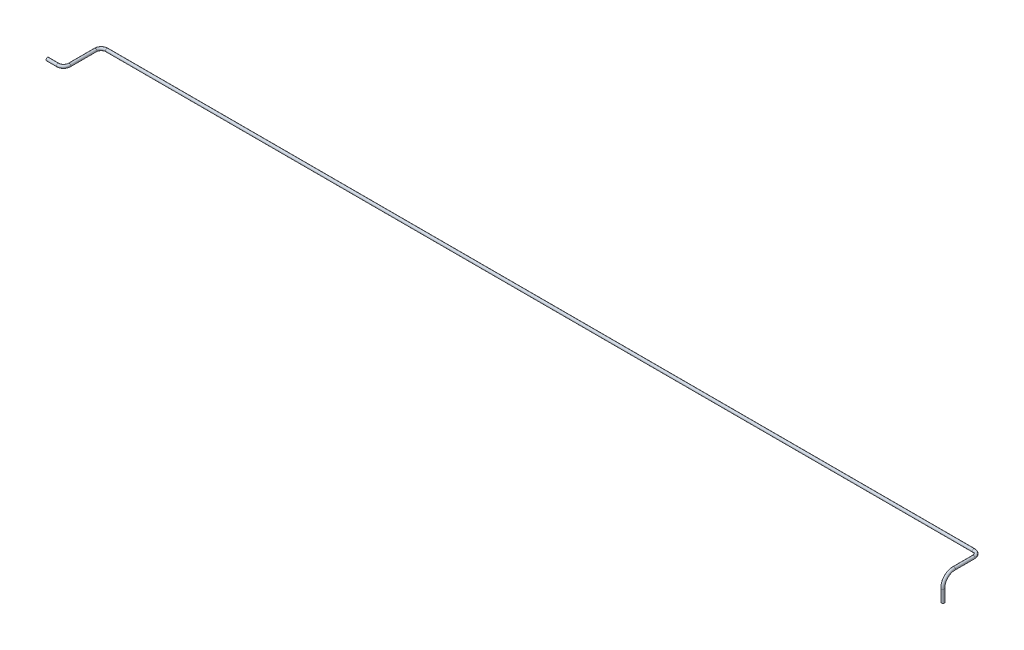
SolidWorks part; units mm, degrees
ref_plane "Front Plane" through (0, 0, 0) normal (0, 0, 1) x (1, 0, 0)
ref_plane "Top Plane" through (0, 0, 0) normal (0, 1, 0) x (1, 0, 0)
ref_plane "Right Plane" through (0, 0, 0) normal (1, 0, 0) x (0, 0, -1)
sketch3d "3DSketch1"
  line L1 (0, 0, 0) -> (22.86, 0, 0)
  line L2 (35.56, 0, -12.7) -> (35.56, 0, -69.85)
  line L3 (48.26, 0, -82.55) -> (1952.9674, 0, -82.55)
  line L4 (1965.6674, 0, -69.85) -> (1965.6674, 0, -26.7385)
  line L5 (1966.5416, -24.9414, -1.3424) -> (1967.4465, -50.7611, -0.8914)
  arc A0 (1965.6674, 0, -69.85) -> (1952.9674, 0, -82.55) centre (1952.9674, 0, -69.85) ccw
  arc A1 (35.56, 0, -69.85) -> (48.26, 0, -82.55) centre (48.26, 0, -69.85) ccw
  arc A2 (22.86, 0, 0) -> (35.56, 0, -12.7) centre (22.86, 0, -12.7) ccw
  arc A3 (1965.6674, 0, -26.7385) -> (1966.5416, -24.9414, -1.3424) centre (1966.5571, -25.3844, -26.7385) ccw
  point P9 (1965.6674, 0, -82.55)
  point P10 (1952.9674, 12.7, -69.85)
  point P12 (1965.6674, 0, -1.778)
  point P16 (35.56, 0, -82.55)
  point P17 (48.26, -12.7, -69.85)
  point P20 (35.56, 0, 0)
  point P22 (22.86, 12.7, -12.7)
  point P23 (1991.9415, -24.4948, -26.7385)
  dimension "D9" = 1968.1014
  dimension "D10" = 25.4
  dimension "D6" = 12.7
  dimension "D7" = 12.7
  dimension "D8" = 91
  dimension "D1" = 35.56
  dimension "D2" = 82.55
  dimension "D3" = 1930.1074
  dimension "D4" = 80.772
  dimension "D5" = 50.8
ref_plane "Plane4" through (0, 0, 0) normal (1, 0, 0) x (0, 0, -1)
sketch "Sketch5" plane through (0, 0, 0) normal (1, 0, 0) x (0, 0, -1)
  circle A0 centre (0, 0) radius 3.175
  circle A1 centre (0, 0) radius 2.667
  dimension "D1" = 6.35
  dimension "D2" = 0.508
sweep "Sweep3" add profiles "Sketch5" path "3DSketch1"
